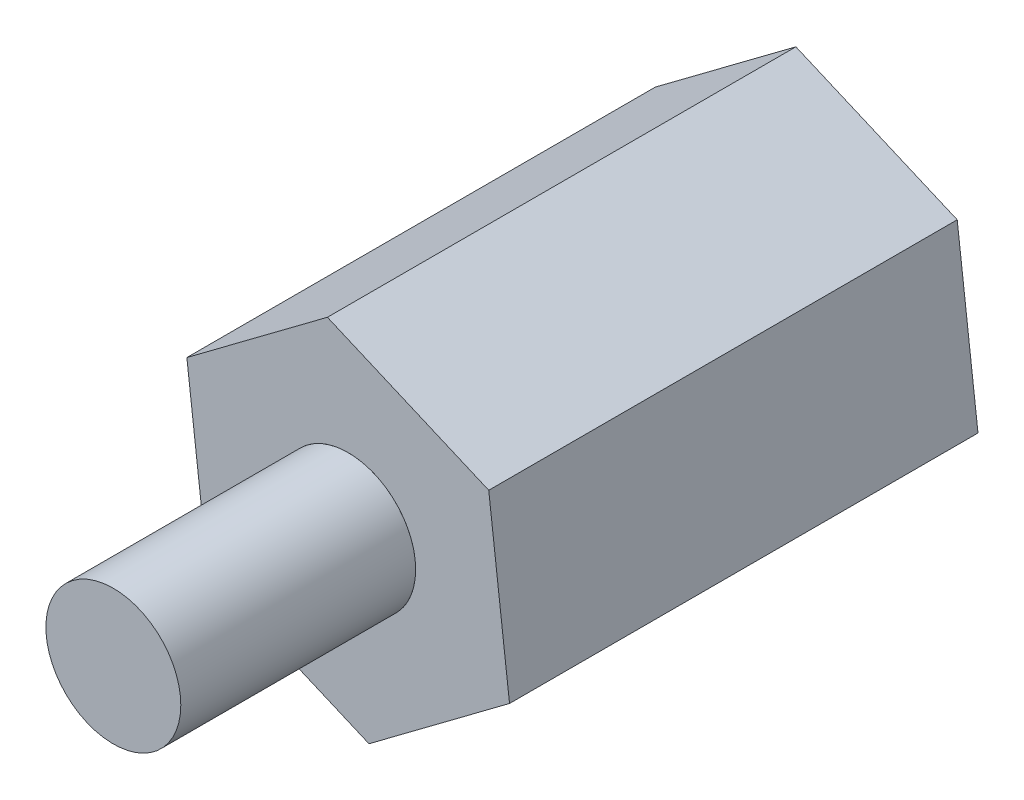
SolidWorks part; units mm, degrees
ref_plane "Front Plane" through (0, 0, 0) normal (0, 0, 1) x (1, 0, 0)
ref_plane "Top Plane" through (0, 0, 0) normal (0, 1, 0) x (1, 0, 0)
ref_plane "Right Plane" through (0, 0, 0) normal (1, 0, 0) x (0, 0, -1)
sketch "Sketch7" plane through (0, 0, 0) normal (0, 0, 1) x (1, 0, 0)
  line L1 (-76.4398, 4.7385) -> (-76.8624, 8.2821)
  line L2 (-76.8624, 8.2821) -> (-80.1426, 9.6879)
  line L3 (-80.1426, 9.6879) -> (-83.0001, 7.5501)
  line L4 (-83.0001, 7.5501) -> (-82.5774, 4.0065)
  line L5 (-82.5774, 4.0065) -> (-79.2973, 2.6007)
  line L6 (-79.2973, 2.6007) -> (-76.4398, 4.7385)
  circle A0 centre (-79.7199, 6.1443) radius 3.0906 construction
  circle A1 centre (-79.7199, 6.1443) radius 1.3716
  dimension "D2" = 2.7432
  dimension "D1" = 7.1374
extrude "Boss-Extrude4" add sketch "Sketch7" along normal mid plane 9.525 separate body
ref_axis "Axis2" through (-79.7199, 6.1443, 11.6672) along (0, 0, -1)
sketch "Sketch8" plane through (0, 0, 4.7625) normal (0, 0, 1) x (1, 0, 0)
  circle A0 centre (-79.7199, 6.1443) radius 1.3716
  dimension "D1" = 2.7432
extrude "Boss-Extrude5" add sketch "Sketch8" along normal blind 4.7752 separate body
equation "\"D2@Sketch7\" = \"screwDiameter\""
equation "\"screwDiameter\"=\"0.108\""
equation "\"standoffHeight\"=\"0.375\""
equation "\"D1@Boss-Extrude4\" = \"standoffHeight\""
equation "\"D1@Sketch8\"=\"screwDiameter\""
